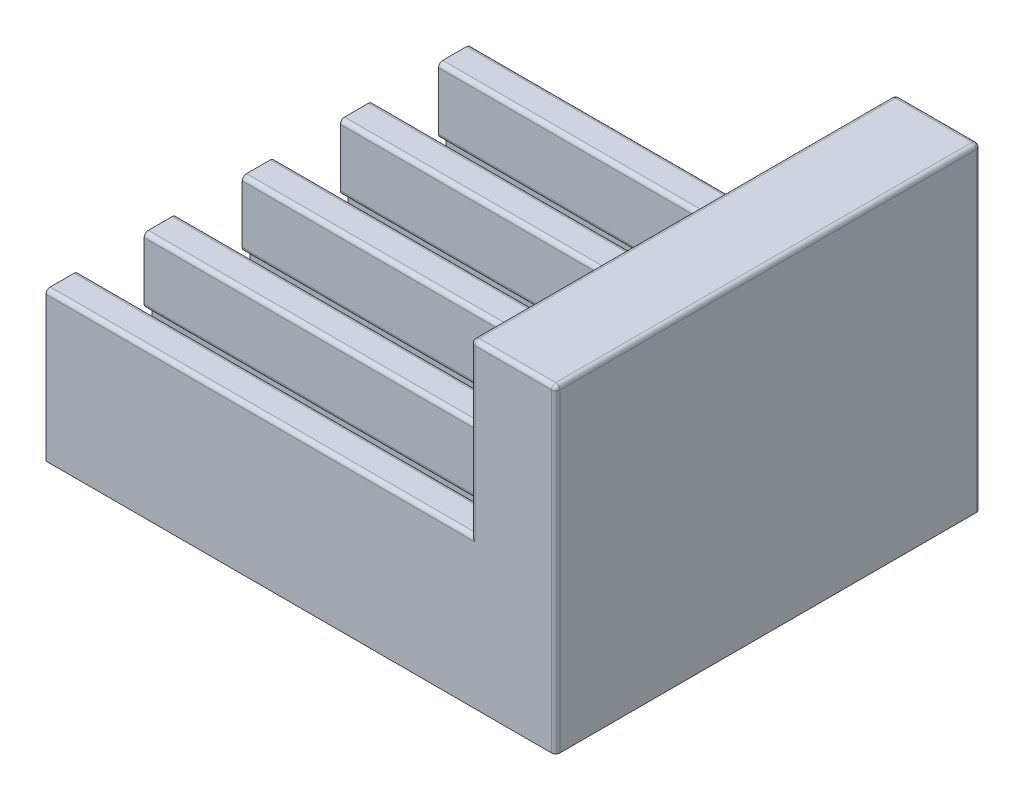
SolidWorks part; units mm, degrees
ref_plane "Front Plane" through (0, 0, 0) normal (0, 0, 1) x (1, 0, 0)
ref_plane "Top Plane" through (0, 0, 0) normal (0, 1, 0) x (1, 0, 0)
ref_plane "Right Plane" through (0, 0, 0) normal (1, 0, 0) x (0, 0, -1)
sketch "Sketch1" plane through (0, 0, 0) normal (0, 1, 0) x (1, 0, 0)
  line L1 (-63.5354, 42.4181) -> (56.4646, 42.4181)
  line L2 (-63.5354, 42.4181) -> (-63.5354, -57.5819)
  line L3 (-63.5354, -57.5819) -> (56.4646, -57.5819)
  line L4 (56.4646, 42.4181) -> (56.4646, -57.5819)
  dimension "D1" = 100
  dimension "D2" = 120
extrude "Boss-Extrude1" add sketch "Sketch1" along normal blind 75
sketch "Sketch2" plane through (0, 75, 0) normal (0, 1, 0) x (1, 0, 0)
  line L0 (-63.5354, -57.5819) -> (56.4646, -57.5819) construction
  line L1 (-63.5354, 42.4181) -> (36.4646, 42.4181)
  line L2 (-63.5354, 42.4181) -> (-63.5354, -57.5819)
  line L3 (-63.5354, -57.5819) -> (36.4646, -57.5819)
  line L4 (36.4646, 42.4181) -> (36.4646, -57.5819)
  dimension "D1" = 100
extrude "Cut-Extrude1" cut sketch "Sketch2" against normal blind 40
sketch "Sketch6" plane through (-63.5354, 0, 0) normal (-1, 0, 0) x (0, 0, 1)
  line L0 (57.5819, 35) -> (-42.4181, 35) construction
  line L1 (-34.8181, 35) -> (-19.3181, 35)
  line L2 (-34.8181, 35) -> (-34.8181, 19.5)
  line L3 (-34.8181, 19.5) -> (-19.3181, 19.5)
  line L4 (-19.3181, 35) -> (-19.3181, 19.5)
  line L5 (-19.3181, 27.25) -> (-11.7181, 27.25) construction
  line L6 (-11.7181, 35) -> (3.7819, 35)
  line L7 (-11.7181, 35) -> (-11.7181, 19.5)
  line L8 (-11.7181, 19.5) -> (3.7819, 19.5)
  line L9 (3.7819, 35) -> (3.7819, 19.5)
  line L10 (11.3819, 35) -> (26.8819, 35)
  line L11 (11.3819, 35) -> (11.3819, 19.5)
  line L12 (11.3819, 19.5) -> (26.8819, 19.5)
  line L13 (26.8819, 35) -> (26.8819, 19.5)
  line L14 (34.4819, 35) -> (49.9819, 35)
  line L15 (34.4819, 35) -> (34.4819, 19.5)
  line L16 (34.4819, 19.5) -> (49.9819, 19.5)
  line L17 (49.9819, 35) -> (49.9819, 19.5)
  line L18 (-15.5181, 27.25) -> (-15.5181, 0) construction
  line L19 (-42.4181, 0) -> (57.5819, 0) construction
  line L20 (7.5819, 35) -> (7.5819, 0) construction
  line L21 (-42.4181, 35) -> (57.5819, 35) construction
  circle A0 centre (-27.0681, 27.25) radius 5.95
  circle A1 centre (-3.9681, 27.25) radius 5.95
  circle A2 centre (42.2319, 27.25) radius 5.95
  circle A3 centre (19.1319, 27.25) radius 5.95
  dimension "D13" = 7.75
  dimension "D1" = 15.5
  dimension "D2" = 15.5
  dimension "D3" = 15.5
  dimension "D4" = 15.5
  dimension "D5" = 15.5
  dimension "D6" = 15.5
  dimension "D7" = 15.5
  dimension "D8" = 15.5
  dimension "D9" = 7.6
  dimension "D10" = 7.6
  dimension "D11" = 7.6
  dimension "D12" = 7.6
  dimension "D14" = 7.75
extrude "Cut-Extrude4" cut sketch "Sketch6" against normal blind 100 contours L11 L10 L13 L12 | L15 L14 L17 L16 | L7 L6 L9 L8 | L2 L1 L4 L3
sketch "Sketch8" plane through (-63.5354, 0, 0) normal (-1, 0, 0) x (0, 0, 1)
  line L1 (-36.6181, 19.5) -> (-17.5181, 19.5)
  line L2 (-36.6181, 19.5) -> (-36.6181, 9.5)
  line L3 (-36.6181, 9.5) -> (-17.5181, 9.5)
  line L4 (-17.5181, 19.5) -> (-17.5181, 9.5)
  line L6 (-15.5181, 35) -> (-15.5181, 0) construction
  line L7 (-19.3181, 35) -> (-11.7181, 35) construction
  line L8 (-42.4181, 0) -> (57.5819, 0) construction
  line L9 (5.5819, 9.5) -> (-13.5181, 9.5)
  line L10 (-13.5181, 19.5) -> (-13.5181, 9.5)
  line L11 (5.5819, 19.5) -> (-13.5181, 19.5)
  line L12 (5.5819, 19.5) -> (5.5819, 9.5)
  line L13 (7.5819, 35) -> (7.5819, 0) construction
  line L14 (11.3819, 35) -> (3.7819, 35) construction
  line L15 (51.7819, 9.5) -> (32.6819, 9.5)
  line L16 (32.6819, 19.5) -> (32.6819, 9.5)
  line L17 (51.7819, 19.5) -> (32.6819, 19.5)
  line L18 (51.7819, 19.5) -> (51.7819, 9.5)
  line L19 (9.5819, 19.5) -> (9.5819, 9.5)
  line L20 (9.5819, 19.5) -> (28.6819, 19.5)
  line L21 (28.6819, 19.5) -> (28.6819, 9.5)
  line L22 (9.5819, 9.5) -> (28.6819, 9.5)
  dimension "D1" = 1.8
  dimension "D2" = 10
  dimension "D3" = 19.1
extrude "Cut-Extrude5" cut sketch "Sketch8" against normal blind 100
extrude "Cut-Extrude6" cut sketch "Sketch6<3>" against normal blind 111 contours A0 | A1 | A3 | A2 region at (-63.5354, 27.25, -27.0681) region at (-63.5354, 27.25, -3.9681) region at (-63.5354, 27.25, 42.2319) region at (-63.5354, 27.25, 19.1319)
sketch "Sketch6<3>" plane through (-63.5354, 0, 0) normal (-1, 0, 0) x (0, 0, 1) same geometry as "Sketch6"
fillet "Fillet1" radius 1 10 edges at (-13.5354, 35, -42.4181) (-13.5354, 35, 57.5819) (36.4646, 55, -42.4181) (36.4646, 55, 57.5819) (46.4646, 75, 57.5819) (36.4646, 75, 7.5819) (46.4646, 75, -42.4181) (56.4646, 75, 7.5819) (56.4646, 37.5, 57.5819) (56.4646, 37.5, -42.4181)
chamfer "Chamfer1" distance 1 angle 45 4 edges at (36.4646, 27.25, 36.2819) (36.4646, 27.25, 13.1819) (36.4646, 27.25, -9.9181) (36.4646, 27.25, -33.0181)
fillet "Fillet2" radius 1 4 edges at (47.4646, 27.25, 48.1819) (47.4646, 27.25, 25.0819) (47.4646, 27.25, 1.9819) (47.4646, 27.25, -21.1181)
fillet "Fillet3" radius 1 16 edges at (-13.5354, 19.5, -19.3181) (-13.5354, 19.5, 3.7819) (-13.5354, 19.5, 26.8819) (-13.5354, 19.5, -34.8181) (-13.5354, 19.5, -11.7181) (-13.5354, 19.5, 11.3819) (-13.5354, 19.5, 34.4819) (-13.5354, 19.5, 49.9819) (-13.5354, 35, -34.8181) (-13.5354, 35, -19.3181) (-13.5354, 35, -11.7181) (-13.5354, 35, 3.7819) (-13.5354, 35, 26.8819) (-13.5354, 35, 11.3819) (-13.5354, 35, 34.4819) (-13.5354, 35, 49.9819)
